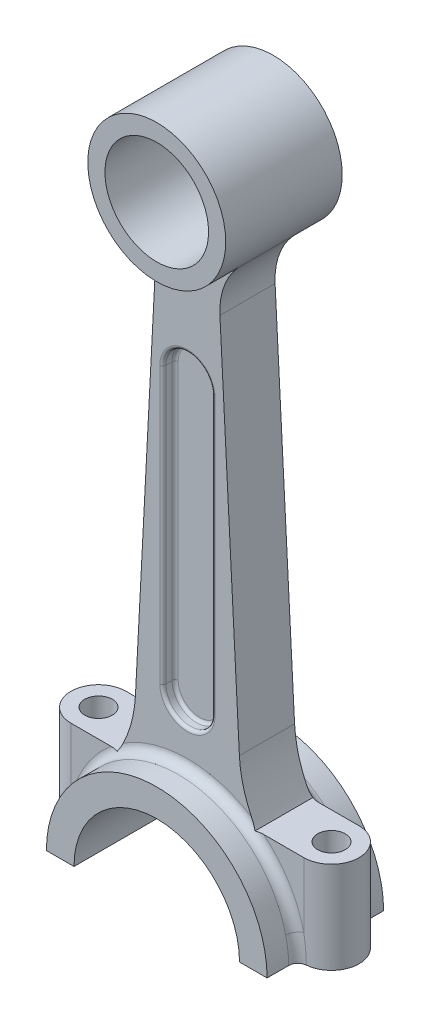
SolidWorks part; units mm, degrees
ref_plane "Alzado" through (0, 0, 0) normal (0, 0, 1) x (1, 0, 0)
ref_plane "Planta" through (0, 0, 0) normal (0, 1, 0) x (1, 0, 0)
ref_plane "Vista lateral" through (0, 0, 0) normal (1, 0, 0) x (0, 0, -1)
sketch "Croquis1" plane through (0, 0, 0) normal (0, 0, 1) x (1, 0, 0)
  line L0 (0, 0) -> (0, -201.2) construction
  line L1 (-10, -20.1556) -> (-17.8497, -169.9368)
  line L2 (10, -20.1556) -> (17.8497, -169.9368)
  line L3 (-36, -201.2) -> (-27, -201.2)
  line L4 (27, -201.2) -> (36, -201.2)
  circle A0 centre (0, 0) radius 16.9
  arc A2 (36, -201.2) -> (-36, -201.2) centre (0, -201.2) ccw
  arc A3 (27, -201.2) -> (-27, -201.2) centre (0, -201.2) ccw
  circle A4 centre (0, 0) radius 22.5
  dimension "D1" = 33.8
  dimension "D2" = 201.2
  dimension "D3" = 45
  dimension "D4" = 54
  dimension "D5" = 72
  dimension "D6" = 20
  dimension "D7" = 6
extrude "Saliente-Extruir1" add sketch "Croquis1" along normal mid plane 38 contours A4 | A0 | A3 | A2 L3
extrude "Saliente-Extruir2" add sketch "Croquis1<4>" along normal mid plane 18 contours A4 L0 A2 L2 | L0 A4 L1 A2 region at (7.1843, -100.8455, 0) region at (-7.1843, -100.8455, 0)
sketch "Croquis1<4>" plane through (0, 0, 0) normal (0, 0, 1) x (1, 0, 0) same geometry as "Croquis1"
sketch "Croquis2" plane through (0, 0, 9) normal (0, 0, 1) x (1, 0, 0)
  line L0 (0, -145.6) -> (0, -55.6) construction
  line L1 (0, 0) -> (0, -201.2) construction
  line L2 (-8, -145.6) -> (-8, -55.6)
  line L3 (8, -145.6) -> (8, -55.6)
  arc A0 (-8, -145.6) -> (8, -145.6) centre (0, -145.6) ccw
  arc A1 (8, -55.6) -> (-8, -55.6) centre (0, -55.6) ccw
  point P4 (0, -100.6)
  dimension "D2" = 8
  dimension "D1" = 90
extrude "Cortar-Extruir1" cut sketch "Croquis2" against normal blind 4
mirror "Simetría1" about plane through (0, 0, 0) normal (0, 0, 1) of "Cortar-Extruir1"
fillet "Redondeo1" radius 1 16 edges at (0, -153.6, 9) (-8, -100.6, 9) (0, -47.6, 9) (0, -153.6, -9) (-8, -100.6, -9) (0, -47.6, -9) (0, -153.6, -5) (-8, -100.6, -5) (0, -47.6, -5) (-8, -100.6, 5) (0, -47.6, 5) (8, -100.6, 5) (0, -153.6, 5) (8, -100.6, 9) (8, -100.6, -9) (8, -100.6, -5)
extrude "Saliente-Extruir3" add sketch "Croquis1<5>" along normal mid plane 38 contours A2 L3 A3 L4
sketch "Croquis1<5>" plane through (0, 0, 0) normal (0, 0, 1) x (1, 0, 0) same geometry as "Croquis1"
fillet "Redondeo2" radius 40 2 edges at (-17.8497, -169.9368, 0) (17.8497, -169.9368, 0)
fillet "Redondeo3" radius 22.5 2 edges at (10, -20.1556, 0) (-10, -20.1556, 0)
ref_plane "Plano1" through (0, -171.2, 0) normal (0, -1, 0) x (-1, 0, 0)
sketch "Croquis3" plane through (0, -171.2, 0) normal (0, -1, 0) x (-1, 0, 0)
  line L0 (38, 0) -> (-38, 0) construction
  line L1 (38, -9) -> (-38, -9)
  line L2 (38, 9) -> (-38, 9)
  arc A0 (38, -9) -> (38, 9) centre (38, 0) ccw
  arc A1 (-38, 9) -> (-38, -9) centre (-38, 0) ccw
  point P2 (0, 0)
  dimension "D2" = 9
  dimension "D1" = 76
extrude "Saliente-Extruir4" add sketch "Croquis3" along normal up to surface (30 mm away) up to face at (-31.5, -201.2, 0)
sketch "Croquis5" plane through (0, 0, 19) normal (0, 0, 1) x (1, 0, 0)
  line L0 (-27, -201.2) -> (27, -201.2) construction
  circle A0 centre (0, -201.2) radius 27
extrude "Cortar-Extruir2" cut sketch "Croquis5" against normal blind 38
sketch "Croquis6" plane through (0, -171.2, 0) normal (0, 1, 0) x (1, 0, 0)
  line L0 (0, -20.9) -> (0, 20.9) construction
  circle A0 centre (38, 0) radius 4.5
  circle A1 centre (-38, 0) radius 4.5
  dimension "D1" = 9
extrude "Cortar-Extruir3" cut sketch "Croquis6" against normal blind 38
fillet "Redondeo4" radius 3 2 edges at (0, -165.2, -9) (0, -165.2, 9)
